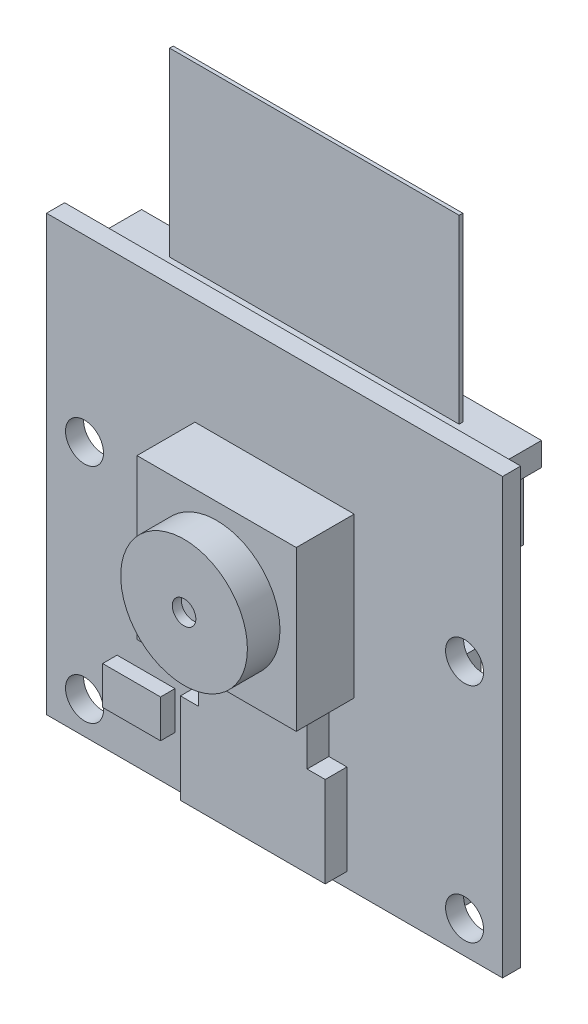
SolidWorks part; units mm, degrees
ref_plane "Přední rovina" through (0, 0, 0) normal (0, 0, 1) x (1, 0, 0)
ref_plane "Horní rovina" through (0, 0, 0) normal (0, 1, 0) x (1, 0, 0)
ref_plane "Pravá rovina" through (0, 0, 0) normal (1, 0, 0) x (0, 0, -1)
sketch "Skica1" plane through (0, 0, 0) normal (0, 0, 1) x (1, 0, 0)
  line L0 (0, -4.05) -> (0, 0) construction
  line L6 (-4.4, -2.7) -> (4.4, -2.7)
  line L7 (-21.3919, 19.9602) -> (21.3919, 19.9602)
  line L8 (-21.3919, 19.9602) -> (-21.3919, -19.9602)
  line L9 (-21.3919, -19.9602) -> (21.3919, -19.9602)
  line L10 (21.3919, 19.9602) -> (21.3919, -19.9602)
  line L11 (-21.3919, 19.9602) -> (21.3919, -19.9602) construction
  line L12 (-21.3919, -19.9602) -> (21.3919, 19.9602) construction
  line L13 (10.5, -10.2) -> (-10.5, -10.2) construction
  line L14 (10.5, -10.2) -> (10.5, 2.1) construction
  line L15 (10.5, 2.1) -> (-10.5, 2.1) construction
  line L16 (-10.5, -10.2) -> (-10.5, 2.1) construction
  line L17 (10.5, -10.2) -> (-10.5, 2.1) construction
  line L18 (10.5, 2.1) -> (-10.5, -10.2) construction
  line L19 (0, -4.05) -> (46.9713, -4.05) construction
  line L20 (-4.4, -2.7) -> (-4.4, 6.1)
  line L21 (12.6, -12) -> (-12.6, -12)
  line L22 (12.6, -12) -> (12.6, 12)
  line L23 (12.6, 12) -> (-12.6, 12)
  line L24 (-12.6, -12) -> (-12.6, 12)
  line L25 (12.6, -12) -> (-12.6, 12) construction
  line L26 (12.6, 12) -> (-12.6, -12) construction
  line L27 (-4.4, 6.1) -> (4.4, 6.1)
  line L28 (4.4, -2.7) -> (4.4, 6.1)
  line L29 (-4.4, -2.7) -> (4.4, 6.1) construction
  line L30 (-4.4, 6.1) -> (4.4, -2.7) construction
  circle A0 centre (-10.5, 2.1) radius 1.05
  circle A1 centre (10.5, 2.1) radius 1.05
  circle A2 centre (10.5, -10.2) radius 1.05
  circle A3 centre (-10.5, -10.2) radius 1.05
  circle A4 centre (0, 1.7) radius 3.5
  point P0 (41.1239, 15.3264)
  point P1 (0, 1.7)
  point P5 (0, 12)
  point P6 (0, 0)
  point P44 (0, 0)
  dimension "D5" = 2.1
  dimension "D6" = 0.75
  dimension "D8" = 7
  dimension "D1" = 25.2
  dimension "D2" = 24
  dimension "D3" = 12.3
  dimension "D4" = 21
  dimension "D7" = 8.8
  dimension "D9" = 5.9
extrude "Přidat vysunutím1" add sketch "Skica1" against normal blind 1 contours L24 L21 L22 L23 A1 A0 L28 L6 L20 L27 A2 A3 | L6 L28 L27 L20 A4 | A4 region at (-4.2755, 1.7, 0) region at (0, -11.652, 0) region at (0, 1.7, 0)
extrude "Přidat vysunutím2" add sketch "Skica1<3>" along normal blind 3.2 contours L6 L28 L27 L20 A4 region at (-4.2755, 1.7, 0)
sketch "Skica1<3>" plane through (0, 0, 0) normal (0, 0, 1) x (1, 0, 0) same geometry as "Skica1"
extrude "Přidat vysunutím3" add sketch "Skica1<4>" along normal blind 5 contours A4 region at (0, 1.7, 0)
sketch "Skica1<4>" plane through (0, 0, 0) normal (0, 0, 1) x (1, 0, 0) same geometry as "Skica1"
sketch "Skica2" plane through (0, 0, 0) normal (0, 0, 1) x (1, 0, 0)
  line L0 (-4.4, -2.7) -> (4.4, -2.7) construction
  line L1 (-4, -11.2) -> (4, -11.2)
  line L2 (-4, -11.2) -> (-4, -6.2)
  line L3 (-4, -6.2) -> (4, -6.2)
  line L4 (4, -11.2) -> (4, -6.2)
  line L5 (-4, -11.2) -> (4, -6.2) construction
  line L6 (-4, -6.2) -> (4, -11.2) construction
  line L7 (-3, -6.2) -> (3, -6.2)
  line L8 (-3, -6.2) -> (-3, -2.7)
  line L9 (-3, -2.7) -> (3, -2.7)
  line L10 (3, -6.2) -> (3, -2.7)
  line L11 (-3, -6.2) -> (3, -2.7) construction
  line L12 (-3, -2.7) -> (3, -6.2) construction
  line L13 (-4.4, -2.7) -> (4.4, -2.7) construction
  point P0 (0, -8.7)
  point P5 (0, -4.45)
  line M18 (4.4, -2.7) -> (-4.4, -2.7)
  dimension "D1" = 8
  dimension "D2" = 5
  dimension "D3" = 8.5
  dimension "D4" = 6
extrude "Přidat vysunutím4" add sketch "Skica2" along normal blind 1.2 contours L1 L4 L3 L2 | L3 L10 L8 M18 region at (0, -8.7, 0) region at (0, -4.45, 0)
sketch "Skica3" plane through (0, 0, -1) normal (0, 0, -1) x (-1, 0, 0)
  line L0 (-12.6, 12) -> (12.6, 12) construction
  line L1 (-10.05, 5.6) -> (10.05, 5.6)
  line L2 (-10.05, 5.6) -> (-10.05, 9.8)
  line L3 (-10.05, 9.8) -> (10.05, 9.8)
  line L4 (10.05, 5.6) -> (10.05, 9.8)
  line L5 (-10.05, 5.6) -> (10.05, 9.8) construction
  line L6 (-10.05, 9.8) -> (10.05, 5.6) construction
  line L7 (-11.05, 9.8) -> (11.05, 9.8)
  line L8 (-11.05, 9.8) -> (-11.05, 11.1)
  line L9 (-11.05, 11.1) -> (11.05, 11.1)
  line L10 (11.05, 9.8) -> (11.05, 11.1)
  line L11 (-11.05, 9.8) -> (11.05, 11.1) construction
  line L12 (-11.05, 11.1) -> (11.05, 9.8) construction
  point P0 (0, 7.7)
  point P5 (0, 10.45)
  dimension "D1" = 22.1
  dimension "D2" = 20.1
  dimension "D3" = 4.2
  dimension "D4" = 1.3
  dimension "D5" = 0.9
extrude "Přidat vysunutím5" add sketch "Skica3" along normal blind 2.7 contours L1 L4 L3 L2 | L7 L10 L9 L8 L3 region at (0, 7.7, -1) region at (0, 10.45, -1)
sketch "Skica4" plane through (0, 0, -1) normal (0, 0, -1) x (-1, 0, 0)
  line L0 (-12.6, -12) -> (12.6, -12) construction
  line L1 (8.8, -11) -> (-9.1, -11)
  line L2 (8.8, -11) -> (8.8, 1)
  line L3 (8.8, 1) -> (-9.1, 1)
  line L4 (-9.1, -11) -> (-9.1, 1)
  line L5 (8.8, -11) -> (-9.1, 1) construction
  line L6 (8.8, 1) -> (-9.1, -11) construction
  line L7 (12.6, -12) -> (12.6, 12) construction
  line L8 (-12.6, -12) -> (-12.6, 12) construction
  point P0 (-0.15, -5)
  dimension "D1" = 1
  dimension "D2" = 3.8
  dimension "D3" = 3.5
  dimension "D4" = 13
extrude "Přidat vysunutím6" add sketch "Skica4" along normal blind 1.3
sketch "Skica5" plane through (0, 0, 0) normal (0, 0, 1) x (1, 0, 0)
  line L0 (-12.6, -12) -> (-12.6, 12) construction
  line L1 (-8.7, -9.3) -> (-5.5, -9.3)
  line L2 (-8.7, -9.3) -> (-8.7, -7.2)
  line L3 (-8.7, -7.2) -> (-5.5, -7.2)
  line L4 (-5.5, -9.3) -> (-5.5, -7.2)
  line L5 (-8.7, -9.3) -> (-5.5, -7.2) construction
  line L6 (-8.7, -7.2) -> (-5.5, -9.3) construction
  line L7 (12.6, -12) -> (-12.6, -12) construction
  point P0 (-7.1, -8.25)
  dimension "D1" = 2.1
  dimension "D2" = 3.2
  dimension "D3" = 3.9
  dimension "D4" = 2.7
extrude "Přidat vysunutím7" add sketch "Skica5" along normal blind 0.8
sketch "Skica6" plane through (0, 0, 5) normal (0, 0, 1) x (1, 0, 0)
  circle A0 centre (0, 1.7) radius 0.65
  dimension "D1" = 1.3
extrude "Odebrat vysunutím1" cut sketch "Skica6" against normal blind 0.5
sketch "Skica7" plane through (0, 11.1, 0) normal (0, 1, 0) x (1, 0, 0)
  line L0 (11.05, 3.7) -> (-11.05, 3.7) construction
  line L1 (8, 2.4) -> (-8, 2.4)
  line L2 (8, 2.4) -> (8, 2.2)
  line L3 (8, 2.2) -> (-8, 2.2)
  line L4 (-8, 2.4) -> (-8, 2.2)
  line L5 (8, 2.4) -> (-8, 2.2) construction
  line L6 (8, 2.2) -> (-8, 2.4) construction
  point P0 (0, 2.3)
  dimension "D1" = 16
  dimension "D2" = 0.2
  dimension "D3" = 1.3
extrude "Přidat vysunutím9" add sketch "Skica7" along normal blind 10
